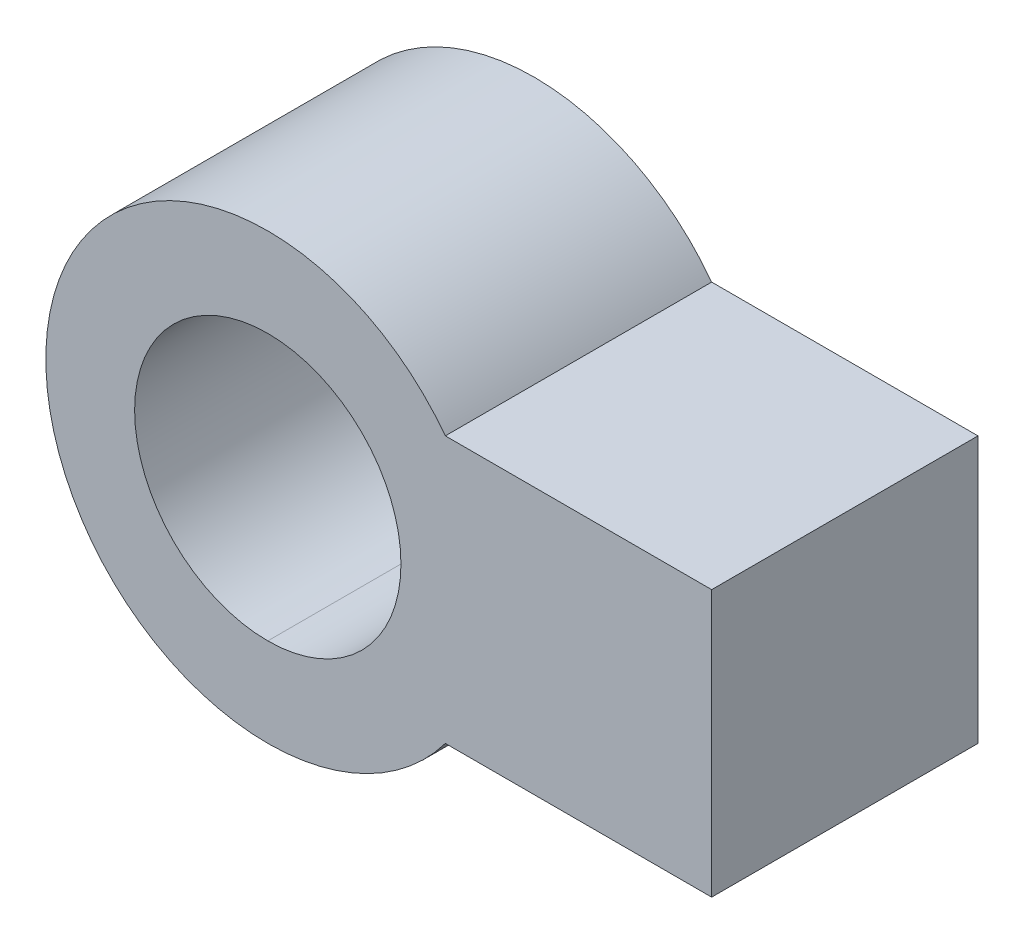
SolidWorks part; units mm, degrees
note: '?' marks a value the reader was unsure of.
ref_plane "Front Plane" through (0, 0, 0) normal (0, 0, 1) x (1, 0, 0)
ref_plane "Top Plane" through (0, 0, 0) normal (0, 1, 0) x (1, 0, 0)
ref_plane "Right Plane" through (0, 0, 0) normal (1, 0, 0) x (0, 0, -1)
sketch "Sketch1" plane through (0, 0, 0) normal (0, 0, 1) x (1, 0, 0)
  line L0 (0, 0) -> (15, 0) construction
  line L5 (0, -3) -> (10, -3)
  line L6 (0, -3) -> (0, 3)
  line L7 (0, 3) -> (10, 3)
  line L8 (10, -3) -> (10, 3)
  circle A0 centre (0, 0) radius 5
  circle A2 centre (0, 0) radius 3
  dimension "D2" = 10
  dimension "D3" = 10
  dimension "D4" = 6
  dimension "D5" = 6
  dimension "D1" = 15
extrude "Boss-Extrude1" add sketch "Sketch1" along normal blind 6
sketch "Sketch2" plane through (10, 0, 0) normal (1, 0, 0) x (0, 0, -1)
  line L0 (-6, 3) -> (0, 3) construction
  line L1 (0, -3) -> (0, 3) construction
  circle A0 centre (-3, 0) radius 2
  point P8 (-3, 0)
  dimension "D3" = 4
  dimension "D1" = 3
  dimension "D2" = 3
ref_axis "Axis1" through (-6.7836, 0, 3) along (1, 0, 0)?
ref_point "Point1"
